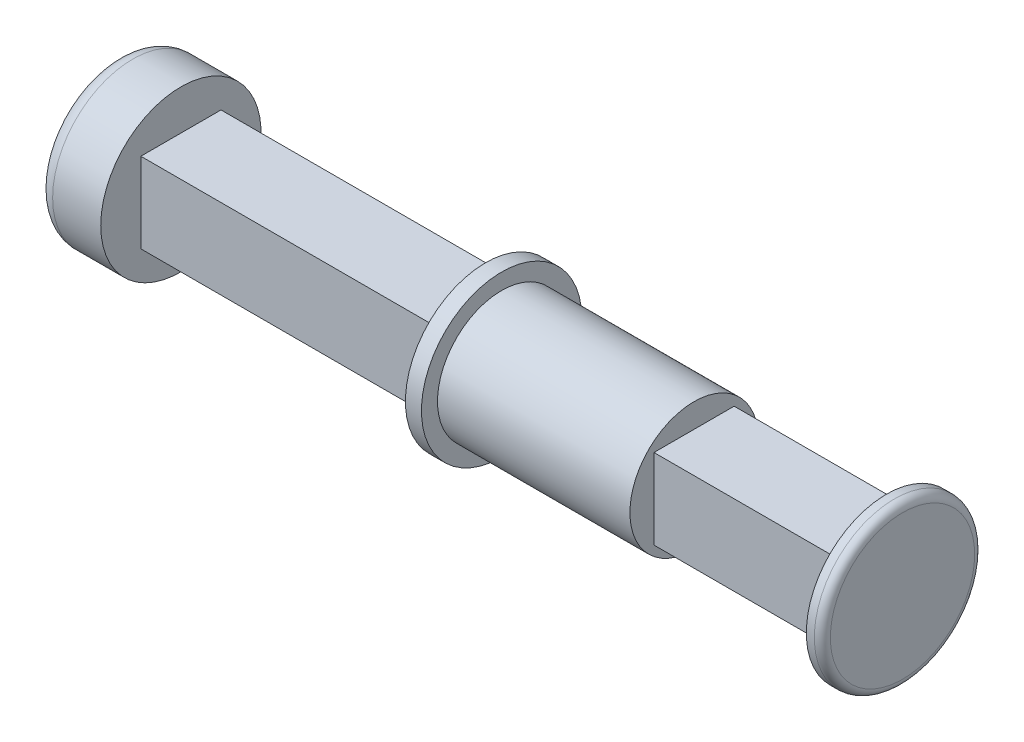
SolidWorks part; units mm, degrees
material "Acciaio al carbonio semplice"
ref_plane "Front Plane" through (0, 0, 0) normal (0, 0, 1) x (1, 0, 0)
ref_plane "Top Plane" through (0, 0, 0) normal (0, 1, 0) x (1, 0, 0)
ref_plane "Right Plane" through (0, 0, 0) normal (1, 0, 0) x (0, 0, -1)
sketch "Sketch1" plane through (0, 0, 0) normal (1, 0, 0) x (0, 0, -1)
  line L0 (25, -25) -> (-25, 25) construction
  line L1 (-25, -25) -> (25, -25)
  line L2 (-25, -25) -> (-25, 25)
  line L3 (-25, 25) -> (25, 25)
  line L4 (25, -25) -> (25, 25)
  line L5 (-25, -25) -> (25, 25) construction
  line L6 (25, 25) -> (-25, -25) construction
  point P0 (0, 0)
  dimension "D2" = 50
  dimension "D3" = 50
extrude "Boss-Extrude1" add sketch "Sketch1" along normal mid plane 190
sketch "Sketch2" plane through (95, 0, 0) normal (1, 0, 0) x (0, 0, -1)
  circle A0 centre (0, 0) radius 50
  dimension "D1" = 100
extrude "Boss-Extrude2" add sketch "Sketch2" along normal blind 10
sketch "Sketch3" plane through (105, 0, 0) normal (1, 0, 0) x (0, 0, -1)
  circle A0 centre (0, 0) radius 40
  dimension "D1" = 80
extrude "Boss-Extrude3" add sketch "Sketch3" along normal blind 120
sketch "Sketch4" plane through (-95, 0, 0) normal (-1, 0, 0) x (0, 0, 1)
  circle A0 centre (0, 0) radius 50
  point P0 (0, 0)
  dimension "D1" = 100
extrude "Boss-Extrude4" add sketch "Sketch4" along normal blind 40
sketch "Schizzo1" plane through (225, 0, 0) normal (1, 0, 0) x (0, 0, -1)
  line L7 (-25, 25) -> (25, 25)
  line L8 (-25, 25) -> (-25, -25)
  line L9 (-25, -25) -> (25, -25)
  line L10 (25, 25) -> (25, -25)
  line L11 (-25, 25) -> (25, -25) construction
  line L12 (-25, -25) -> (25, 25) construction
  point P0 (0, 0)
  point P5 (0, 0)
  dimension "D1" = 50
extrude "Boss-Extrude5" add sketch "Schizzo1" along normal blind 120
fillet "Raccordo1" radius 10 1 edges at (-135, 0, 50)
sketch "Schizzo2" plane through (345, 0, 0) normal (1, 0, 0) x (0, 0, -1)
  circle A0 centre (0, 0) radius 50
extrude "Estrusione-Estrusione1" add sketch "Schizzo2" along normal blind 10
fillet "Raccordo2" radius 5 1 edges at (355, 0, -50)
